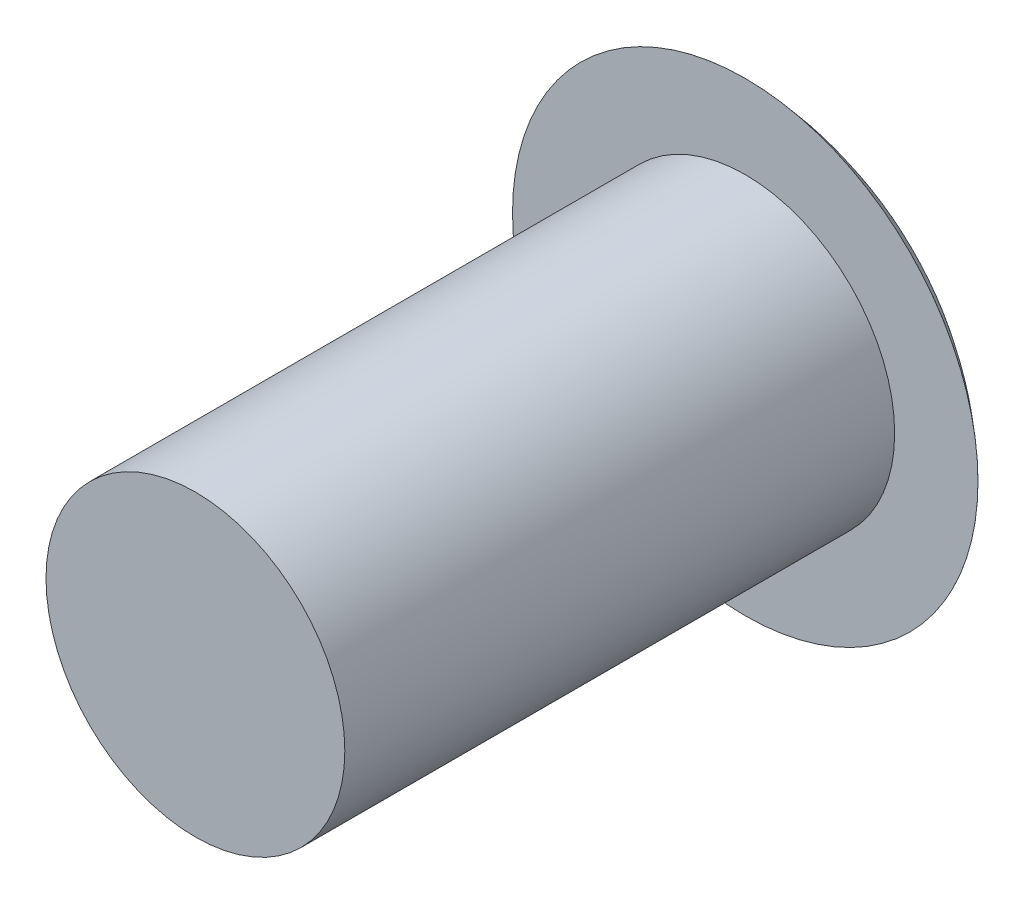
SolidWorks part; units mm, degrees
ref_plane "Front Plane" through (0, 0, 0) normal (0, 0, 1) x (1, 0, 0)
ref_plane "Top Plane" through (0, 0, 0) normal (0, 1, 0) x (1, 0, 0)
ref_plane "Right Plane" through (0, 0, 0) normal (1, 0, 0) x (0, 0, -1)
sketch "Sketch1" plane through (0, 0, 0) normal (0, 0, 1) x (1, 0, 0)
  circle A0 centre (0, 0) radius 5
  dimension "D1" = 10
extrude "Boss-Extrude1" add sketch "Sketch1" along normal mid plane 18.4
sketch "Sketch2" plane through (0, 0, -9.2) normal (0, 0, -1) x (-1, 0, 0)
  circle A0 centre (0, 0) radius 7.7882
extrude "Boss-Extrude2" add sketch "Sketch2" along normal blind 0.001
dome "Dome1" faces to dome 1 distance 3 reverse direction no elliptical dome no face at (-7.7882, 0, -9.201) parameters "D1"=3
sketch "Sketch3" plane through (0, 0, 0) normal (0, 0, 1) x (1, 0, 0)
  line L1 (-3.3125, 0) -> (-1.6563, -2.8687)
  line L2 (-1.6563, -2.8687) -> (1.6563, -2.8687)
  line L3 (1.6563, -2.8687) -> (3.3125, 0)
  line L4 (3.3125, 0) -> (1.6563, 2.8687)
  line L5 (1.6563, 2.8687) -> (-1.6563, 2.8687)
  line L6 (-1.6563, 2.8687) -> (-3.3125, 0)
  circle A0 centre (0, 0) radius 2.8687 construction
extrude "Cut-Extrude1" cut sketch "Sketch3" against normal blind 40 from offset 10 offset against normal yes
chamfer "Chamfer2" distance 0.2 angle 45 6 edges at (0, 2.8687, -11.841) (2.4844, 1.4344, -11.841) (2.4844, -1.4344, -11.841) (0, -2.8687, -11.841) (-2.4844, -1.4344, -11.841) (-2.4844, 1.4344, -11.841) first distance on face at (0, 0, -11.841)
scale "Scale1" scale about centroid uniform scaling yes scale factor 1.9329
scale "Scale2" scale about centroid uniform scaling yes scale factor 1.5
